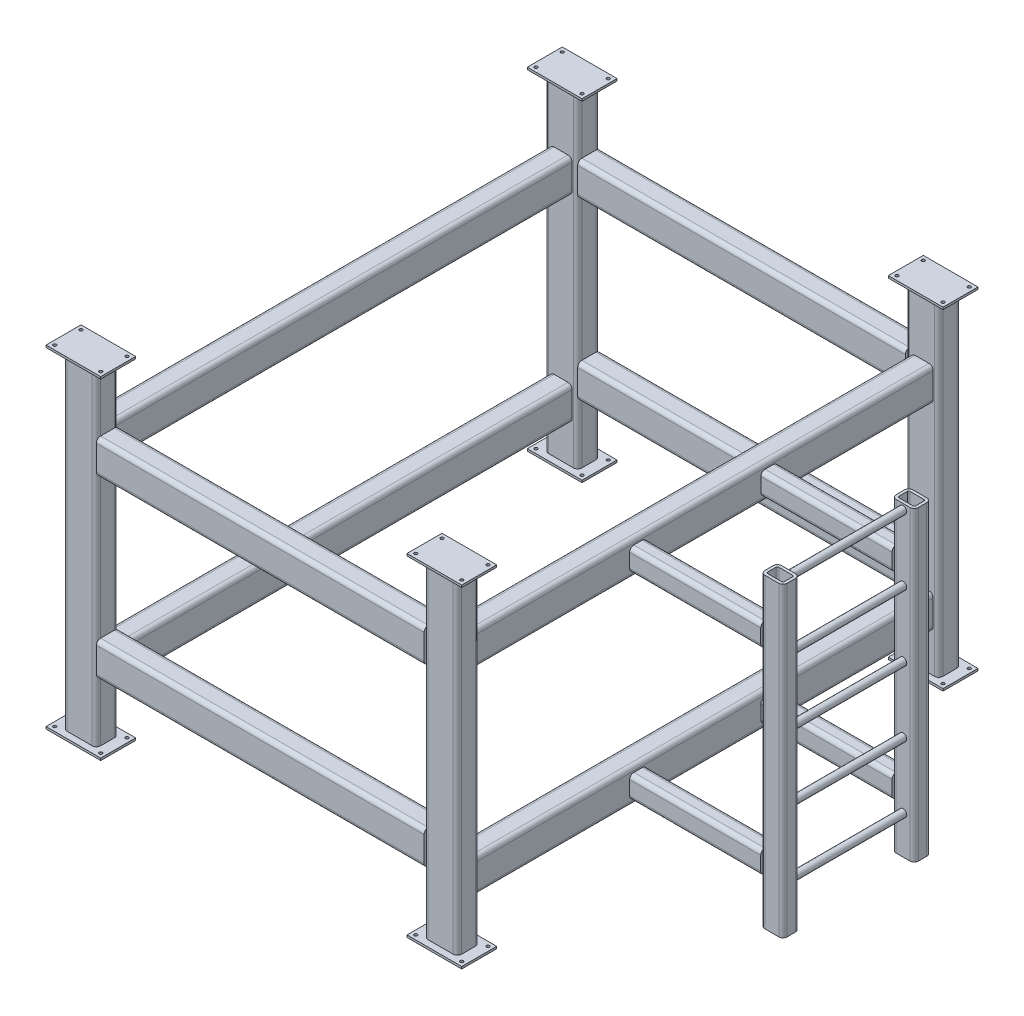
SolidWorks part; units mm, degrees
note: The reader was unsure of these and kept them because the rebuilt part matched: shared geometry of "Sketch14<2>".
ref_plane "Front Plane" through (0, 0, 0) normal (0, 0, 1) x (1, 0, 0)
ref_plane "Top Plane" through (0, 0, 0) normal (0, 1, 0) x (1, 0, 0)
ref_plane "Right Plane" through (0, 0, 0) normal (1, 0, 0) x (0, 0, -1)
sketch "Sketch2" plane through (0, 0, 0) normal (0, 1, 0) x (1, 0, 0)
  line L0 (0, 1100) -> (0, -1100) construction
  line L1 (-825, -1100) -> (825, -1100) construction
  line L2 (-825, -1100) -> (-825, 1100) construction
  line L3 (-825, 1100) -> (825, 1100) construction
  line L4 (825, -1100) -> (825, 1100) construction
  line L5 (-825, -1100) -> (825, 1100) construction
  line L6 (-825, 1100) -> (825, -1100) construction
  point P0 (0, 0)
  dimension "D1" = 1650
  dimension "D2" = 2200
sketch3d "3DSketch1"
  line L0 (-825, 0, 1100) -> (-825, 1500, 1100)
  line L1 (-825, 0, -1100) -> (-825, 1500, -1100)
  line L2 (825, 0, 1100) -> (825, 1500, 1100)
  line L3 (825, 0, -1100) -> (825, 1500, -1100)
  line L4 (-825, 1150, 1100) -> (-825, 1150, -1100)
  line L5 (-825, 250, 1100) -> (-825, 250, -1100)
  line L6 (825, 1150, 1100) -> (825, 1150, -1100)
  line L7 (825, 250, 1100) -> (825, 250, -1100)
  line L8 (-825, 1150, 1100) -> (825, 1150, 1100)
  line L9 (-825, 1150, -1100) -> (825, 1150, -1100)
  line L10 (-825, 350, 1100) -> (825, 350, 1100)
  line L11 (-825, 350, -1100) -> (825, 350, -1100)
  dimension "D4" = 350
  dimension "D1" = 1500
  dimension "D2" = 350
  dimension "D3" = 900
other "Rectangular tube 6 X 4 X 0.5(1)"
ref_plane "Plane1" through (-825, 0, 1100) normal (0, 1, 0) x (0, 0, -1)
sketch "Sketch1" plane through (-825, 0, 1100) normal (0, 1, 0) x (0, 0, -1)
  line L0 (-31.75, -63.5) -> (31.75, -63.5)
  line L1 (-38.1, -57.15) -> (-38.1, 57.15)
  line L2 (31.75, 63.5) -> (-31.75, 63.5)
  line L3 (38.1, 57.15) -> (38.1, -57.15)
  line L4 (-31.75, -76.2) -> (31.75, -76.2)
  line L5 (-50.8, -57.15) -> (-50.8, 57.15)
  line L6 (31.75, 76.2) -> (-31.75, 76.2)
  line L7 (50.8, 57.15) -> (50.8, -57.15)
  line L8 (0, 0) -> (50.8, 0) construction
  line L9 (0, 0) -> (0, 76.2) construction
  arc A0 (50.8, 57.15) -> (31.75, 76.2) centre (31.75, 57.15) ccw
  arc A1 (31.75, -76.2) -> (50.8, -57.15) centre (31.75, -57.15) ccw
  arc A2 (-50.8, -57.15) -> (-31.75, -76.2) centre (-31.75, -57.15) ccw
  arc A3 (-31.75, 76.2) -> (-50.8, 57.15) centre (-31.75, 57.15) ccw
  arc A4 (-31.75, 63.5) -> (-38.1, 57.15) centre (-31.75, 57.15) ccw
  arc A5 (38.1, 57.15) -> (31.75, 63.5) centre (31.75, 57.15) ccw
  arc A6 (31.75, -63.5) -> (38.1, -57.15) centre (31.75, -57.15) ccw
  arc A7 (-38.1, -57.15) -> (-31.75, -63.5) centre (-31.75, -57.15) ccw
  point P3 (0, -76.2)
  point P4 (-50.8, 0)
  point P5 (0, 0)
  point P6 (50.8, -76.2)
  point P7 (-50.8, -76.2)
  point P8 (-50.8, 76.2)
  point P33 (0, 0)
  point P35 (50.8, 76.2)
  point P36 (50.8, 0)
  point P37 (0, 76.2)
  dimension "D1" = 19.05
  dimension "Thickness" = 12.7
  dimension "V_leg" = 152.4
  dimension "H_leg" = 101.6
other "Rectangular tube 6 X 4 X 0.5(2)"
ref_plane "Plane2" through (-825, 1150, 1100) normal (0, 0, -1) x (1, 0, 0)
sketch "Sketch11" plane through (-825, 1150, 1100) normal (0, 0, -1) x (1, 0, 0)
  line L0 (-31.75, -63.5) -> (31.75, -63.5)
  line L1 (-38.1, -57.15) -> (-38.1, 57.15)
  line L2 (31.75, 63.5) -> (-31.75, 63.5)
  line L3 (38.1, 57.15) -> (38.1, -57.15)
  line L4 (-31.75, -76.2) -> (31.75, -76.2)
  line L5 (-50.8, -57.15) -> (-50.8, 57.15)
  line L6 (31.75, 76.2) -> (-31.75, 76.2)
  line L7 (50.8, 57.15) -> (50.8, -57.15)
  line L8 (0, 0) -> (50.8, 0) construction
  line L9 (0, 0) -> (0, 76.2) construction
  arc A0 (50.8, 57.15) -> (31.75, 76.2) centre (31.75, 57.15) ccw
  arc A1 (31.75, -76.2) -> (50.8, -57.15) centre (31.75, -57.15) ccw
  arc A2 (-50.8, -57.15) -> (-31.75, -76.2) centre (-31.75, -57.15) ccw
  arc A3 (-31.75, 76.2) -> (-50.8, 57.15) centre (-31.75, 57.15) ccw
  arc A4 (-31.75, 63.5) -> (-38.1, 57.15) centre (-31.75, 57.15) ccw
  arc A5 (38.1, 57.15) -> (31.75, 63.5) centre (31.75, 57.15) ccw
  arc A6 (31.75, -63.5) -> (38.1, -57.15) centre (31.75, -57.15) ccw
  arc A7 (-38.1, -57.15) -> (-31.75, -63.5) centre (-31.75, -57.15) ccw
  point P3 (0, -76.2)
  point P4 (-50.8, 0)
  point P5 (0, 0)
  point P6 (50.8, -76.2)
  point P7 (-50.8, -76.2)
  point P8 (-50.8, 76.2)
  point P33 (0, 0)
  point P35 (50.8, 76.2)
  point P36 (50.8, 0)
  point P37 (0, 76.2)
  dimension "D1" = 19.05
  dimension "Thickness" = 12.7
  dimension "V_leg" = 152.4
  dimension "H_leg" = 101.6
other "Rectangular tube 6 X 4 X 0.5(5)"
ref_plane "Plane3" through (-825, 1150, 1100) normal (1, 0, 0) x (0, 0, -1)
sketch "Sketch13" plane through (-825, 1150, 1100) normal (1, 0, 0) x (0, 0, -1)
  line L0 (-31.75, -63.5) -> (31.75, -63.5)
  line L1 (-38.1, -57.15) -> (-38.1, 57.15)
  line L2 (31.75, 63.5) -> (-31.75, 63.5)
  line L3 (38.1, 57.15) -> (38.1, -57.15)
  line L4 (-31.75, -76.2) -> (31.75, -76.2)
  line L5 (-50.8, -57.15) -> (-50.8, 57.15)
  line L6 (31.75, 76.2) -> (-31.75, 76.2)
  line L7 (50.8, 57.15) -> (50.8, -57.15)
  line L8 (0, 0) -> (50.8, 0) construction
  line L9 (0, 0) -> (0, 76.2) construction
  arc A0 (50.8, 57.15) -> (31.75, 76.2) centre (31.75, 57.15) ccw
  arc A1 (31.75, -76.2) -> (50.8, -57.15) centre (31.75, -57.15) ccw
  arc A2 (-50.8, -57.15) -> (-31.75, -76.2) centre (-31.75, -57.15) ccw
  arc A3 (-31.75, 76.2) -> (-50.8, 57.15) centre (-31.75, 57.15) ccw
  arc A4 (-31.75, 63.5) -> (-38.1, 57.15) centre (-31.75, 57.15) ccw
  arc A5 (38.1, 57.15) -> (31.75, 63.5) centre (31.75, 57.15) ccw
  arc A6 (31.75, -63.5) -> (38.1, -57.15) centre (31.75, -57.15) ccw
  arc A7 (-38.1, -57.15) -> (-31.75, -63.5) centre (-31.75, -57.15) ccw
  point P3 (0, -76.2)
  point P4 (-50.8, 0)
  point P5 (0, 0)
  point P6 (50.8, -76.2)
  point P7 (-50.8, -76.2)
  point P8 (-50.8, 76.2)
  point P33 (0, 0)
  point P35 (50.8, 76.2)
  point P36 (50.8, 0)
  point P37 (0, 76.2)
  dimension "D1" = 19.05
  dimension "Thickness" = 12.7
  dimension "V_leg" = 152.4
  dimension "H_leg" = 101.6
other "Trim/Extend1"
sketch "Sketch14" plane through (0, 1500, 0) normal (0, 1, 0) x (1, 0, 0)
  line L0 (-901.2, -1100) -> (-748.8, -1100) construction
  line L1 (-901.2, -1068.25) -> (-901.2, -1131.75) construction
  line L2 (-748.8, -1131.75) -> (-748.8, -1068.25) construction
  line L3 (0, 0) -> (-1566.0728, 0) construction
  line L4 (-950, -1020) -> (-700, -1020)
  line L5 (-950, -1020) -> (-950, -1180)
  line L6 (-950, -1180) -> (-700, -1180)
  line L7 (-700, -1020) -> (-700, -1180)
  line L8 (-950, -1020) -> (-700, -1180) construction
  line L9 (-950, -1180) -> (-700, -1020) construction
  line L10 (-930, -1040) -> (-720, -1040) construction
  line L11 (-930, -1040) -> (-930, -1160) construction
  line L12 (-930, -1160) -> (-720, -1160) construction
  line L13 (-720, -1040) -> (-720, -1160) construction
  line L14 (-930, -1040) -> (-720, -1160) construction
  line L15 (-930, -1160) -> (-720, -1040) construction
  line L16 (0, 0) -> (0, -1567.72) construction
  line L17 (930, -1160) -> (720, -1040) construction
  line L18 (930, -1040) -> (720, -1160) construction
  line L19 (720, -1040) -> (720, -1160) construction
  line L20 (930, -1160) -> (720, -1160) construction
  line L21 (930, -1040) -> (930, -1160) construction
  line L22 (930, -1040) -> (720, -1040) construction
  line L23 (950, -1180) -> (700, -1020) construction
  line L24 (950, -1020) -> (700, -1180) construction
  line L25 (901.2, -1100) -> (748.8, -1100) construction
  line L26 (700, -1020) -> (700, -1180)
  line L27 (950, -1180) -> (700, -1180)
  line L28 (950, -1020) -> (950, -1180)
  line L29 (950, -1020) -> (700, -1020)
  line L30 (901.2, 1100) -> (748.8, 1100) construction
  line L31 (950, 1020) -> (700, 1180) construction
  line L32 (950, 1180) -> (700, 1020) construction
  line L33 (930, 1040) -> (720, 1040) construction
  line L34 (930, 1040) -> (930, 1160) construction
  line L35 (930, 1160) -> (720, 1160) construction
  line L36 (720, 1040) -> (720, 1160) construction
  line L37 (930, 1040) -> (720, 1160) construction
  line L38 (930, 1160) -> (720, 1040) construction
  line L39 (-930, 1160) -> (-720, 1040) construction
  line L40 (-930, 1040) -> (-720, 1160) construction
  line L41 (-720, 1040) -> (-720, 1160) construction
  line L42 (-930, 1160) -> (-720, 1160) construction
  line L43 (-930, 1040) -> (-930, 1160) construction
  line L44 (-930, 1040) -> (-720, 1040) construction
  line L45 (-950, 1180) -> (-700, 1020) construction
  line L46 (-950, 1020) -> (-700, 1180) construction
  line L47 (-901.2, 1100) -> (-748.8, 1100) construction
  line L48 (950, 1020) -> (700, 1020)
  line L49 (950, 1020) -> (950, 1180)
  line L50 (950, 1180) -> (700, 1180)
  line L51 (700, 1020) -> (700, 1180)
  line L52 (-700, 1020) -> (-700, 1180)
  line L53 (-950, 1180) -> (-700, 1180)
  line L54 (-950, 1020) -> (-950, 1180)
  line L55 (-950, 1020) -> (-700, 1020)
  circle A0 centre (-930, -1040) radius 7
  circle A1 centre (-720, -1040) radius 7
  circle A2 centre (-720, -1160) radius 7
  circle A3 centre (-930, -1160) radius 7
  circle A4 centre (930, -1160) radius 7
  circle A5 centre (720, -1160) radius 7
  circle A6 centre (720, -1040) radius 7
  circle A7 centre (930, -1040) radius 7
  circle A8 centre (930, 1040) radius 7
  circle A9 centre (720, 1040) radius 7
  circle A10 centre (720, 1160) radius 7
  circle A11 centre (930, 1160) radius 7
  circle A12 centre (-930, 1160) radius 7
  circle A13 centre (-720, 1160) radius 7
  circle A14 centre (-720, 1040) radius 7
  circle A15 centre (-930, 1040) radius 7
  point P6 (-825, -1100)
  point P11 (-825, -1100)
  point P38 (825, -1100)
  point P67 (825, 1100)
  point P68 (-825, 1100)
  dimension "D5" = 14
  dimension "D1" = 250
  dimension "D2" = 160
  dimension "D3" = 210
  dimension "D4" = 120
extrude "Boss-Extrude1" add sketch "Sketch14" along normal blind 10 separate body
extrude "Boss-Extrude2" add sketch "Sketch14<2>" against normal blind 10 from surface at -1500 separate body starting at face at (825, 0, 1100)
sketch "Sketch14<2>" plane through (0, 1500, 0) normal (0, 1, 0) x (1, 0, 0) same geometry as "Sketch14"
sketch "Sketch15" plane through (875.8, 0, 0) normal (1, 0, 0) x (0, 0, -1)
  line L1 (-300, 250) -> (300, 250) construction
  line L2 (-300, 250) -> (-300, 1150) construction
  line L3 (-300, 1150) -> (300, 1150) construction
  line L4 (300, 250) -> (300, 1150) construction
  line L5 (-300, 250) -> (300, 1150) construction
  line L6 (-300, 1150) -> (300, 250) construction
  line L7 (-1049.2, 1207.15) -> (-1049.2, 1092.85) construction
  line L8 (-1049.2, 307.15) -> (-1049.2, 192.85) construction
  point P0 (0, 700)
  point P10 (-1049.2, 1150)
  point P13 (-1049.2, 250)
  dimension "D1" = 600
sketch3d "3DSketch2"
  line L0 (875.8, 1150, -300) -> (1525.8, 1150, -300)
  line L1 (875.8, 250, 300) -> (875.8, 1150, -300) construction
  line L2 (875.8, 250, -300) -> (875.8, 1150, -300) construction
  line L3 (875.8, 250, 300) -> (1525.8, 250, 300)
  line L4 (875.8, 1150, 300) -> (1525.8, 1150, 300)
  line L5 (1525.8, 1400, 300) -> (1525.8, 0, 300)
  line L6 (875.8, 250, -300) -> (1525.8, 250, -300)
  line L8 (1525.8, 1400, -300) -> (1525.8, 0, -300)
  dimension "D1" = 650
  dimension "D2" = 1400
  dimension "D3" = 250
other "Rectangular tube 4 X 3 X 0.25(1)"
ref_plane "Plane4" through (875.8, 1150, 300) normal (1, 0, 0) x (0, 0, -1)
sketch "Sketch110" plane through (875.8, 1150, 300) normal (1, 0, 0) x (0, 0, -1)
  line L0 (-19.05, -38.1) -> (19.05, -38.1)
  line L1 (-25.4, -31.75) -> (-25.4, 31.75)
  line L2 (19.05, 38.1) -> (-19.05, 38.1)
  line L3 (25.4, 31.75) -> (25.4, -31.75)
  line L4 (-19.05, -50.8) -> (19.05, -50.8)
  line L5 (-38.1, -31.75) -> (-38.1, 31.75)
  line L6 (19.05, 50.8) -> (-19.05, 50.8)
  line L7 (38.1, 31.75) -> (38.1, -31.75)
  line L8 (0, 0) -> (38.1, 0) construction
  line L9 (0, 0) -> (0, 50.8) construction
  arc A0 (38.1, 31.75) -> (19.05, 50.8) centre (19.05, 31.75) ccw
  arc A1 (19.05, -50.8) -> (38.1, -31.75) centre (19.05, -31.75) ccw
  arc A2 (-38.1, -31.75) -> (-19.05, -50.8) centre (-19.05, -31.75) ccw
  arc A3 (-19.05, 50.8) -> (-38.1, 31.75) centre (-19.05, 31.75) ccw
  arc A4 (-19.05, 38.1) -> (-25.4, 31.75) centre (-19.05, 31.75) ccw
  arc A5 (25.4, 31.75) -> (19.05, 38.1) centre (19.05, 31.75) ccw
  arc A6 (19.05, -38.1) -> (25.4, -31.75) centre (19.05, -31.75) ccw
  arc A7 (-25.4, -31.75) -> (-19.05, -38.1) centre (-19.05, -31.75) ccw
  point P3 (0, -50.8)
  point P4 (-38.1, 0)
  point P5 (0, 0)
  point P6 (38.1, -50.8)
  point P7 (-38.1, -50.8)
  point P8 (-38.1, 50.8)
  point P33 (0, 0)
  point P35 (38.1, 50.8)
  point P36 (38.1, 0)
  point P37 (0, 50.8)
  dimension "D1" = 19.05
  dimension "Thickness" = 12.7
  dimension "V_leg" = 101.6
  dimension "H_leg" = 76.2
sketch3d "3DSketch3"
  line L0 (1525.8, 1400, -261.9) -> (1525.8, 1375, -261.9) construction
  line L1 (1557.55, 1400, -261.9) -> (1494.05, 1400, -261.9) construction
  line L2 (1525.8, 1400, 261.9) -> (1525.8, 1375, 261.9) construction
  line L3 (1494.05, 1400, 261.9) -> (1557.55, 1400, 261.9) construction
  line L5 (1525.8, 1375, -261.9) -> (1525.8, 1375, 261.9)
  dimension "D1" = 25
other "Pipe 1.0 SCH 40(1)"
ref_plane "Plane5" through (1525.8, 1375, -261.9) normal (0, 0, 1) x (1, 0, 0)
sketch "Sketch111" plane through (1525.8, 1375, -261.9) normal (0, 0, 1) x (1, 0, 0)
  circle A0 centre (0, 0) radius 13.3223
  circle A1 centre (0, 0) radius 16.7005
  circle A2 centre (0, 0) radius 12.7 construction
  point P5 (0, 16.7005)
  point P6 (0, -16.7005)
  point P7 (-16.7005, 0)
  point P8 (16.7005, 0)
  point P9 (0, 0)
  dimension "In_dia" = 26.6446
  dimension "Out_dia" = 33.401
  dimension "D1" = 25.4
pattern_linear "LPattern1" count 5 spacing 300 along (0, -1, 0) of bodies 135
equation "\"D4@3DSketch1\"=\"D2@3DSketch1\""
